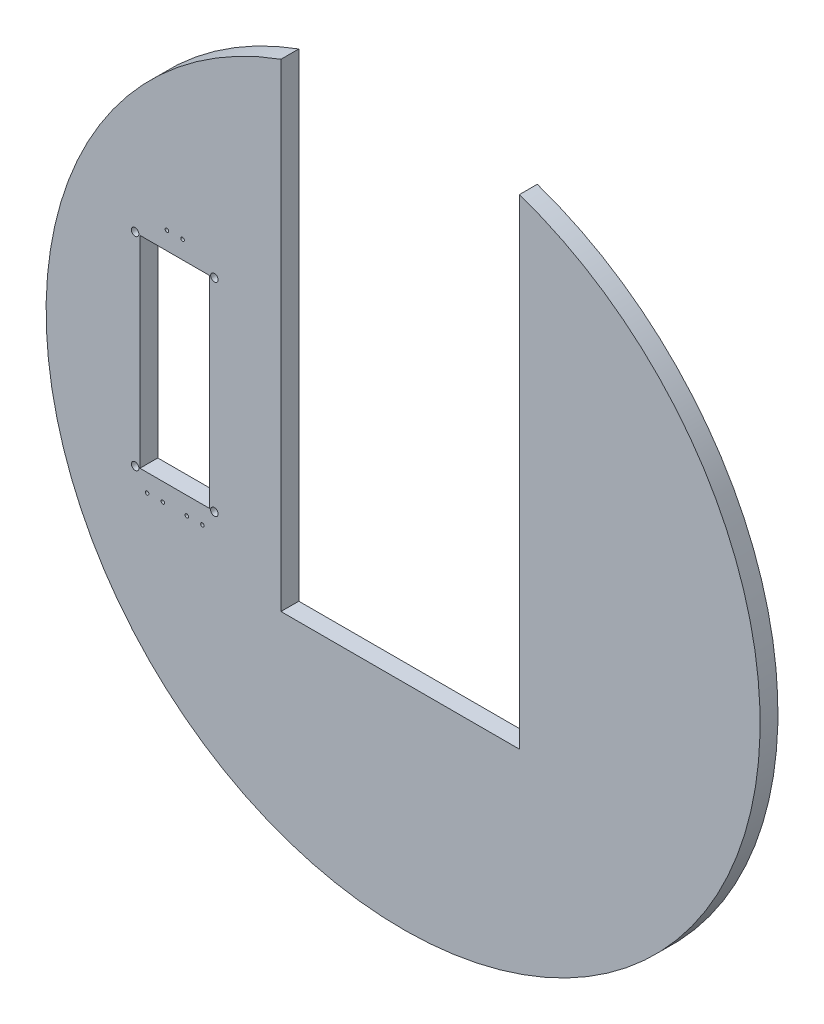
SolidWorks part; units mm, degrees
ref_plane "Front Plane" through (0, 0, 0) normal (0, 0, 1) x (1, 0, 0)
ref_plane "Top Plane" through (0, 0, 0) normal (0, 1, 0) x (1, 0, 0)
ref_plane "Right Plane" through (0, 0, 0) normal (1, 0, 0) x (0, 0, -1)
sketch "Sketch1" plane through (0, 0, 0) normal (0, 0, 1) x (1, 0, 0)
  line L0 (-57.15, -6.35) -> (57.15, -6.35) construction
  line L1 (41.3872, -6.35) -> (-43.4488, -6.35)
  line L2 (41.3872, -6.35) -> (41.3872, 92.71)
  line L3 (41.3872, 92.71) -> (-43.4488, 92.71)
  line L4 (-43.4488, -6.35) -> (-43.4488, 92.71)
  line L5 (-32.7808, 92.71) -> (-37.8608, 92.71) construction
  line L6 (41.3872, 92.71) -> (41.3872, 164.5171)
  line L7 (-43.4488, 92.71) -> (-43.4488, 163.7865)
  line L8 (40.8792, -3.81) -> (40.8792, 9.8425) construction
  line L9 (-42.9408, 9.8425) -> (-42.9408, -3.81) construction
  circle A0 centre (0, 44.45) radius 85.725 construction
  circle A1 centre (0, 44.45) radius 85.725 construction
  arc A2 (-43.4488, 163.7865) -> (41.3872, 164.5171) centre (0, 44.45) ccw
  dimension "D1" = 254
  dimension "D2" = 0.508
  dimension "D3" = 0.508
extrude "Boss-Extrude1" add sketch "Sketch1" along normal blind 6.35 contours L7 A2 L6 L2 L1 L4 region at (44.9306, 43.18, 0)
sketch "Sketch2" plane through (0, 0, 0) normal (0, 0, -1) x (-1, 0, 0)
  line L0 (43.4488, -6.35) -> (43.4488, 163.7865) construction
  line L1 (68.8488, 12.7) -> (93.6138, 12.7)
  line L2 (68.8488, 12.7) -> (68.8488, 84.455)
  line L3 (68.8488, 84.455) -> (93.6138, 84.455)
  line L4 (93.6138, 12.7) -> (93.6138, 84.455)
  line L5 (68.8488, 12.7) -> (93.6138, 84.455) construction
  line L6 (68.8488, 84.455) -> (93.6138, 12.7) construction
  line L7 (-41.3872, -6.35) -> (43.4488, -6.35) construction
  line L8 (67.1343, 12.5095) -> (95.3283, 12.5095) construction
  line L9 (67.1343, 12.5095) -> (67.1343, 84.6455) construction
  line L10 (67.1343, 84.6455) -> (95.3283, 84.6455) construction
  line L11 (95.3283, 84.6455) -> (95.3283, 12.5095) construction
  line L12 (95.3283, 84.6455) -> (67.1343, 12.5095) construction
  line L13 (95.3283, 12.5095) -> (67.1343, 84.6455) construction
  circle A0 centre (67.1343, 12.5095) radius 1.3335
  circle A1 centre (67.1343, 84.6455) radius 1.3335
  circle A2 centre (95.3283, 84.6455) radius 1.3335
  circle A3 centre (95.3283, 12.5095) radius 1.3335
  point P0 (81.2313, 48.5775)
  point P5 (81.2313, 48.5775)
  dimension "D5" = 2.667
  dimension "D6" = 2.667
  dimension "D7" = 2.667
  dimension "D8" = 2.667
  dimension "D1" = 24.765
  dimension "D2" = 71.755
  dimension "D3" = 25.4
  dimension "D4" = 19.05
  dimension "D9" = 28.194
  dimension "D10" = 72.136
extrude "Cut-Extrude1" cut sketch "Sketch2" against normal up to next
sketch "Sketch3" plane through (0, 0, 6.35) normal (0, 0, 1) x (1, 0, 0)
  line L0 (-71.3888, 6.35) -> (-76.9768, 6.35) construction
  line L1 (-68.8488, 12.7) -> (-93.6138, 12.7) construction
  line L2 (-68.8488, 84.455) -> (-68.8488, 12.7) construction
  line L3 (-85.4858, 6.35) -> (-91.0738, 6.35) construction
  line L4 (-93.6138, 12.7) -> (-93.6138, 84.455) construction
  line L5 (-78.4373, 90.805) -> (-84.0253, 90.805) construction
  line L6 (-93.6138, 84.455) -> (-68.8488, 84.455) construction
  circle A0 centre (-71.3888, 6.35) radius 0.635
  circle A1 centre (-76.9768, 6.35) radius 0.635
  circle A2 centre (-85.4858, 6.35) radius 0.635
  circle A3 centre (-91.0738, 6.35) radius 0.635
  circle A4 centre (-78.4373, 90.805) radius 0.635
  circle A5 centre (-84.0253, 90.805) radius 0.635
  point P4 (-73.2665, 4.6144)
  dimension "D1" = 1.27
  dimension "D2" = 1.27
  dimension "D6" = 1.27
  dimension "D7" = 1.27
  dimension "D11" = 1.27
  dimension "D12" = 1.27
  dimension "D15" = 9.5885
  dimension "D3" = 5.588
  dimension "D4" = 6.35
  dimension "D5" = 2.54
  dimension "D8" = 5.588
  dimension "D9" = 2.54
  dimension "D10" = 6.35
  dimension "D13" = 5.588
  dimension "D14" = 6.35
extrude "Cut-Extrude2" cut sketch "Sketch3" against normal up to next
